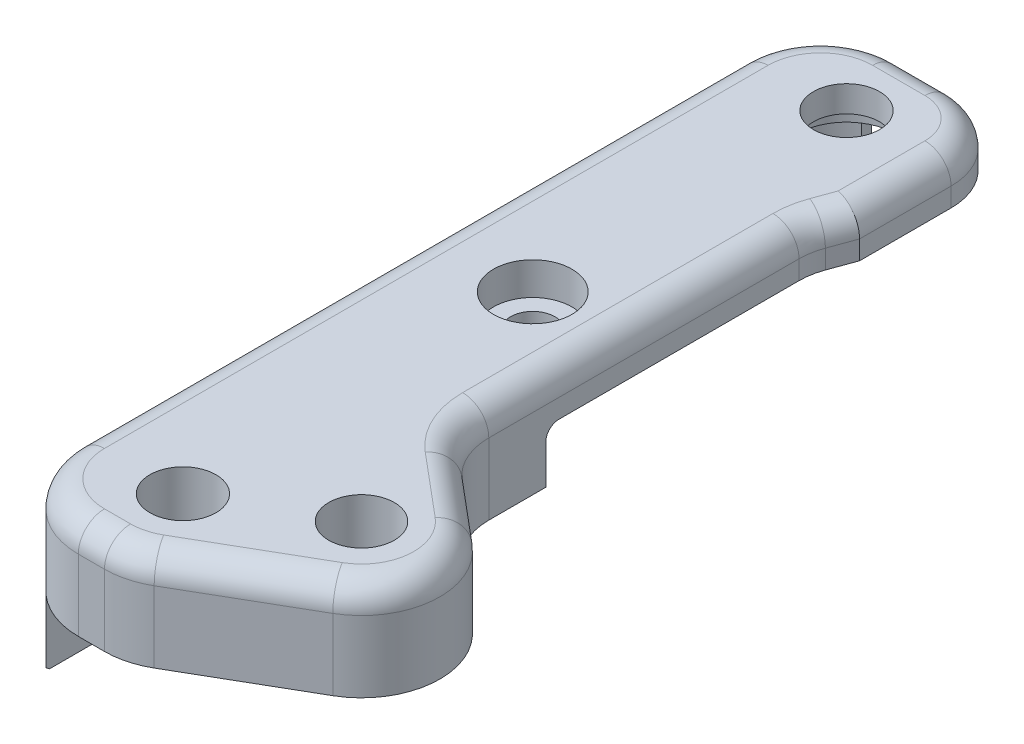
SolidWorks part; units mm, degrees
ref_plane "前视基准面" through (0, 0, 0) normal (0, 0, 1) x (1, 0, 0)
ref_plane "上视基准面" through (0, 0, 0) normal (0, 1, 0) x (1, 0, 0)
ref_plane "右视基准面" through (0, 0, 0) normal (1, 0, 0) x (0, 0, -1)
other "Configuration Table"
sketch "草图1" plane through (0, 0, 0) normal (0, 1, 0) x (1, 0, 0)
  line L0 (0, 0) -> (0, 50.7543) construction
  line L1 (-8, -6) -> (-8, 56.7543)
  line L2 (-8, 56.7543) -> (7, 56.7543)
  line L3 (7, 56.7543) -> (7, 44.7543)
  line L4 (7, 44.7543) -> (6, 42.0068)
  line L5 (6, 42.0068) -> (6, 15.0647)
  line L8 (0, -6) -> (-8, -6)
  line L9 (8.6603, 5) -> (0, 0) construction
  line L10 (18.5622, 5) -> (8.6603, 5) construction
  line L11 (11.6603, -0.1962) -> (3, -5.1962)
  line L12 (6, 15.0647) -> (12.517, 9.5963)
  circle A1 centre (0, 0) radius 2.525
  circle A2 centre (0, 50.7543) radius 2.525
  circle A3 centre (8.6603, 5) radius 2.505
  arc A4 (11.6603, -0.1962) -> (12.517, 9.5963) centre (8.6603, 5) ccw
  arc A5 (0, -6) -> (3, -5.1962) centre (0, 0) ccw
  dimension "D1" = 5.05
  dimension "D3" = 5.05
  dimension "D9" = 5.01
  dimension "D8" = 12
  dimension "D14" = 12
  dimension "D2" = 50.7543
  dimension "D4" = 6
  dimension "D5" = 6
  dimension "D6" = 8
  dimension "D7" = 7
  dimension "D10" = 30
  dimension "D11" = 14
  dimension "D12" = 12
  dimension "D13" = 10
  dimension "D15" = 20
  dimension "D16" = 50
extrude "凸台-拉伸1" add sketch "草图1" along normal blind 25
ref_plane "基准面2" through (0, 12.5, 0) normal (0, -1, 0) x (-1, 0, 0)
sketch "草图6" plane through (0, 12.5, 0) normal (0, -1, 0) x (-1, 0, 0)
  line L0 (8, 56.7543) -> (8, -6) construction
  line L1 (-7, 56.7543) -> (3.8, 56.7543)
  line L2 (-7, 56.7543) -> (-7, 21.7543)
  line L3 (-7, 21.7543) -> (3.8, 21.7543)
  line L4 (3.8, 56.7543) -> (3.8, 21.7543)
  dimension "D1" = 4.2
  dimension "D2" = 35
extrude "切除-拉伸2" cut sketch "草图6" against normal mid plane 18.1
sketch "草图5" plane through (0, 12.5, 0) normal (0, -1, 0) x (-1, 0, 0)
  line L0 (8, -6) -> (0, -6) construction
  line L1 (-19, 24) -> (6, 24)
  line L2 (-19, 24) -> (-19, -6)
  line L3 (-19, -6) -> (6, -6)
  line L4 (6, 24) -> (6, -6)
  line L5 (8, 56.7543) -> (8, -6) construction
  dimension "D1" = 2
  dimension "D2" = 30
  dimension "D3" = 25
extrude "切除-拉伸1" cut sketch "草图5" against normal mid plane 10.1
fillet "圆角2" radius 6 2 edges at (-8, 12.5, 6) (-8, 12.5, -56.7543)
sketch "草图7" plane through (0, 7.45, 0) normal (0, 1, 0) x (1, 0, 0)
  circle A0 centre (0, 0) radius 5
  circle A1 centre (0, 0) radius 2.5
  dimension "D1" = 10
  dimension "D2" = 5
sketch "草图8" plane through (0, 17.55, 0) normal (0, -1, 0) x (1, 0, 0)
  circle A0 centre (0, 0) radius 5
  circle A1 centre (0, 0) radius 2.5
  dimension "D1" = 10
  dimension "D2" = 5
fillet "圆角4" radius 5 6 edges at (7, 1.725, -56.7543) (7, 23.275, -56.7543) (6, 3.725, -15.0647) (6, 1.725, -42.0068) (6, 23.275, -42.0068) (6, 21.275, -15.0647)
fillet "圆角7" radius 2 30 edges at (7, 0, -48.2543) (5.5355, 0, -55.2898) (0, 0, -56.7543) (-6.2426, 0, -54.997) (10.1515, 0, -11.5811) (14.6374, 0, -4.4771) (7.3301, 0, 2.6962) (1.5529, 0, 5.7956) (-1, 0, 6) (-6.2426, 0, 4.2426) (7, 25, -48.2543) (5.5355, 25, -55.2898) (0, 25, -56.7543) (-6.2426, 25, -54.997) (10.1515, 25, -11.5811) (14.6374, 25, -4.4771) (7.3301, 25, 2.6962) (1.5529, 25, 5.7956) (-1, 25, 6) (-6.2426, 25, 4.2426) (6.6508, 0, -43.7948) (-8, 0, -25.3772) (6, 0, -29.2607) (6.6508, 25, -43.7948) (6, 25, -29.2607) (-8, 25, -25.3772) (6.4685, 0, -15.2831) (6.076, 0, -41.9934) (6.076, 25, -41.9934) (6.4685, 25, -15.2831)
sketch "草图9" plane through (-6, 0, 0) normal (1, 0, 0) x (0, 0, -1)
  line L0 (13.566, 17.55) -> (9.5963, 17.55) construction
  line L1 (8, 17.55) -> (12, 17.55)
  line L2 (8, 17.55) -> (8, 7.45)
  line L3 (8, 7.45) -> (12, 7.45)
  line L4 (12, 17.55) -> (12, 7.45)
  line L5 (17.3962, 7.45) -> (13.566, 7.45) construction
  line L6 (24, 17.55) -> (24, 7.45) construction
  dimension "D1" = 12
  dimension "D2" = 4
extrude "凸台-拉伸4" add sketch "草图9" along normal blind 10
ref_plane "基准面3" through (0, 12.5, 0) normal (0, -1, 0) x (-1, 0, 0)
fillet "圆角8" radius 1 8 edges at (1.1, 3.45, -21.7543) (-1, 7.45, -12) (-4.9, 7.45, -24) (-1, 7.45, -8) (-1, 17.55, -8) (1.1, 21.55, -21.7543) (-1, 17.55, -12) (-4.9, 17.55, -24)
sketch "草图11" plane through (0, 12.5, 0) normal (0, -1, 0) x (-1, 0, 0)
  line L1 (-26.7164, 62.0414) -> (24.7804, 62.0414)
  line L2 (-26.7164, 62.0414) -> (-26.7164, -8.5902)
  line L3 (-26.7164, -8.5902) -> (24.7804, -8.5902)
  line L4 (24.7804, 62.0414) -> (24.7804, -8.5902)
extrude "切除-拉伸5" cut sketch "草图11" against normal blind 22
chamfer "倒角1" distance 0.2 angle 45 3 edges at (-7.4772, 12.5, 2.4495) (-6.8374, 12.5, -54.304) (-8, 12.5, -25.3772)
sketch "草图14" plane through (0, 12.5, 0) normal (0, 1, 0) x (1, 0, 0)
  circle A0 centre (0, 50.7543) radius 6.25
  dimension "D1" = 12.5
extrude "切除-拉伸8" cut sketch "草图14" against normal up to surface (9.05 mm away) up to face at (0, 3.45, -53.2793)
sketch "草图16" plane through (0, 3.45, 0) normal (0, 1, 0) x (1, 0, 0)
  line L1 (-3.8, 45.7922) -> (-3.8, 24) construction
  line L2 (-3.8, 50.7543) -> (-3.8, 30.7543)
  line L3 (-3.8, 22.7543) -> (-3.8, 45.7922) construction
  line L4 (-3.8, 30.7543) -> (-2.5, 30.7543)
  line L5 (-2.5, 30.7543) -> (-2.5, 47.8925)
  arc A0 (-2.5, 47.8925) -> (-3.8, 50.7543) centre (0, 50.7543) ccw
  dimension "D1" = 1.3
  dimension "D2" = 20
extrude "切除-拉伸9" cut sketch "草图16" against normal blind 1.45
fillet "圆角9" radius 0.5 1 edges at (-2.5, 2.725, -47.8925)
fillet "圆角10" radius 0.5 2 edges at (-2.5, 2.725, -30.7543) (-3.8, 2.725, -30.7543)
mirror "镜向1" about plane through (0, 12.5, 0) normal (0, -1, 0) of bodies 120
sketch "草图17" plane through (0, 0, -56.7543) normal (0, 0, -1) x (-1, 0, 0)
  line L1 (-33.7754, 12.5) -> (40.4394, 12.5)
  line L2 (-33.7754, 12.5) -> (-33.7754, -15.2972)
  line L3 (-33.7754, -15.2972) -> (40.4394, -15.2972)
  line L4 (40.4394, 12.5) -> (40.4394, -15.2972)
  line L5 (3.8, 12.5) -> (7.8, 12.5) construction
extrude "切除-拉伸10" cut sketch "草图17" against normal blind 93
sketch "草图18" plane through (0, 21.55, 0) normal (0, -1, 0) x (1, 0, 0)
  line L1 (6, -21.7543) -> (-3.8, -21.7543) construction
  line L3 (0, -50.7543) -> (0, 0) construction
  circle A0 centre (0, -26.7543) radius 1.7
  dimension "D3" = 3.4
  dimension "D1" = 5
extrude "切除-拉伸11" cut sketch "草图18" against normal blind 10
sketch "草图19" plane through (0, 25, 0) normal (0, 1, 0) x (1, 0, 0)
  circle A0 centre (0, 26.7543) radius 3
  dimension "D1" = 6
extrude "切除-拉伸12" cut sketch "草图19" against normal blind 2.5
equation "\"0。2\"=1"
